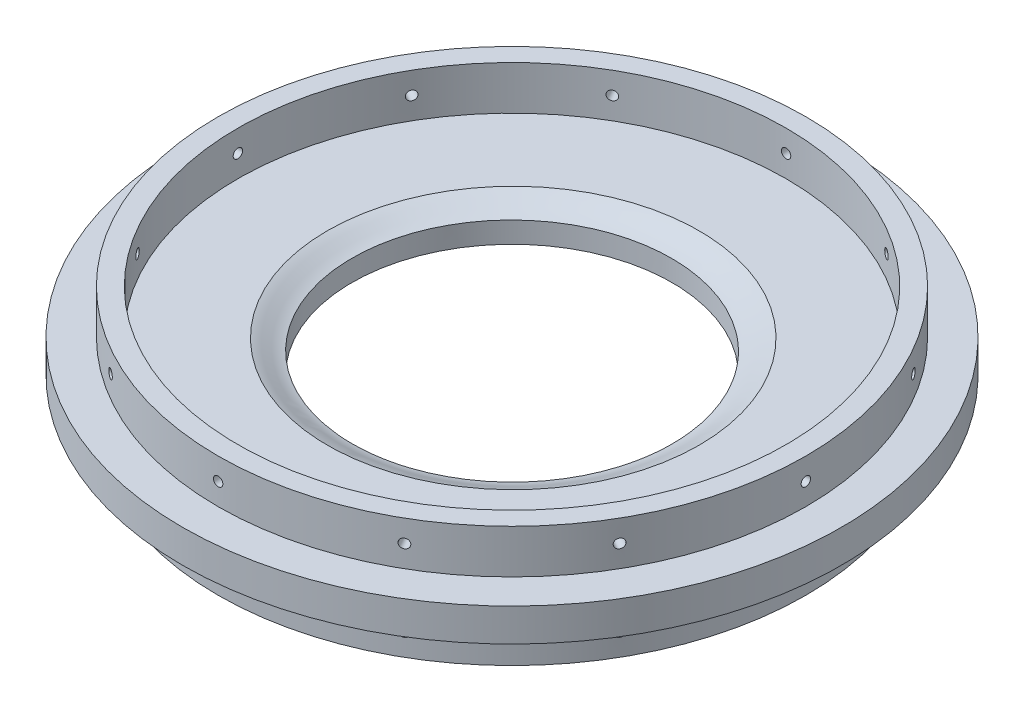
SolidWorks part; units mm, degrees
material "6061-T6 (SS)"
ref_plane "Front Plane" through (0, 0, 0) normal (0, 0, 1) x (1, 0, 0)
ref_plane "Top Plane" through (0, 0, 0) normal (0, 1, 0) x (1, 0, 0)
ref_plane "Right Plane" through (0, 0, 0) normal (1, 0, 0) x (0, 0, -1)
sketch "Sketch1" plane through (0, 0, 0) normal (0, 1, 0) x (1, 0, 0)
  line L5 (0, 0) -> (127.635, 0)
  line L6 (0, 0) -> (0, 127.635)
  line L7 (0, 127.635) -> (127.635, 127.635)
  line L8 (127.635, 0) -> (127.635, 127.635)
  dimension "D1" = 127.635
  dimension "D2" = 127.635
extrude "Boss-Extrude1" add sketch "Sketch1" along normal blind 9.525 contours L5 L8 L7 L6
sketch "Sketch12" plane through (0, 0, 0) normal (0, -1, 0) x (1, 0, 0)
  line L0 (63.8175, 0) -> (63.8175, -127.635) construction
  line L1 (0, 0) -> (127.635, 0) construction
  line L2 (0, -127.635) -> (127.635, -127.635) construction
  line L3 (0, -63.8175) -> (127.635, -63.8175) construction
  line L4 (0, 0) -> (0, -127.635) construction
  line L5 (127.635, 0) -> (127.635, -127.635) construction
  circle A0 centre (63.8175, -63.8175) radius 95.4151
  dimension "D1" = 190.8302
extrude "Boss-Extrude2" add sketch "Sketch12" against normal up to surface (9.525 mm away) contours A0 up to face at (63.8175, 9.525, -63.8175)
sketch "Sketch5" plane through (0, 9.525, 0) normal (0, 1, 0) x (1, 0, 0)
  circle A0 centre (63.8175, 63.8175) radius 46.355
  circle A3 centre (63.8175, 63.8175) radius 95.4151 construction
  dimension "D1" = 92.71
extrude "Cut-Extrude1" cut sketch "Sketch5" against normal blind 9.525
sketch "Sketch14" plane through (0, 9.525, 0) normal (0, -1, 0) x (1, 0, 0)
  line L0 (63.8175, -63.8175) -> (147.6375, -63.8175) construction
  line L1 (0, -19.2087) -> (0, 19.2087) construction
  line L2 (147.6375, -63.8175) -> (152.7175, -63.8175)
  line L3 (136.3808, -105.7742) -> (140.8401, -108.2104)
  circle A0 centre (63.8175, -63.8175) radius 46.355 construction
  arc A2 (147.6375, -63.8175) -> (136.3808, -105.7742) centre (63.8175, -63.8175) cw
  arc A3 (152.7175, -63.8175) -> (140.8401, -108.2104) centre (63.8175, -63.8175) cw
  point P0 (63.8175, -63.8175)
  dimension "D1" = 83.82
  dimension "D2" = 88.9
  dimension "D3" = 46.482
  dimension "D4" = 43.942
ref_plane "Support mirror reference plane" through (0, 4.7625, 0) normal (0, 1, 0) x (1, 0, 0)
sketch "Sketch25" plane through (0, 9.525, 0) normal (0, -1, 0) x (1, 0, 0)
  line L0 (63.8175, -63.8175) -> (123.0872, -4.5478) construction
  line L2 (123.0872, -4.5478) -> (126.6793, -0.9557)
  line L3 (144.7953, -42.1754) -> (149.6712, -40.7448)
  line L5 (63.8175, -63.8175) -> (147.6375, -63.8175) construction
  arc A2 (123.0872, -4.5478) -> (144.7953, -42.1754) centre (63.8175, -63.8175) cw
  arc A3 (126.6793, -0.9557) -> (149.6712, -40.7448) centre (63.8175, -63.8175) cw
  point P0 (63.8175, -63.8175)
  dimension "D1" = 83.82
  dimension "D2" = 88.9
  dimension "D3" = 46.482
  dimension "D4" = 43.942
  dimension "D5" = 45
sketch "Sketch30" plane through (0, 0, 0) normal (0, -1, 0) x (1, 0, 0)
  circle A0 centre (63.8175, -63.8175) radius 85.09
  circle A1 centre (63.8175, -63.8175) radius 79.375
  dimension "D1" = 170.18
  dimension "D2" = 158.75
extrude "Boss-Extrude3" add sketch "Sketch30" along normal blind 12.7
mirror "Mirror1" about plane through (0, 4.7625, 0) normal (0, 1, 0) of "Boss-Extrude3"
sketch "Sketch31" plane through (0, 0, 0) normal (0, -1, 0) x (-1, 0, 0)
  line L0 (-63.8175, -52.481) -> (-63.8175, 177.7216) construction
ref_plane "Plane1" through (0, 0, -148.9075) normal (0, 0, -1) x (-1, 0, 0)
ref_plane "Plane2" through (63.8175, 0, 0) normal (-1, 0, 0) x (0, 0, -1)
sketch "Sketch32" plane through (0, 0, -148.9075) normal (0, 0, -1) x (-1, 0, 0)
  line L4 (-63.8175, -87.3125) -> (-63.8175, 87.3125) construction
  line L5 (-148.9075, 0) -> (21.2725, 0) construction
  line L6 (21.2725, 9.525) -> (-148.9075, 9.525) construction
  circle A0 centre (-63.8175, -6.35) radius 1.3526
  circle A1 centre (-63.8175, 15.875) radius 1.3525
  dimension "D1" = 2.7051
  dimension "D2" = 2.7051
  dimension "D3" = 6.35
  dimension "D4" = 6.35
extrude "Cut-Extrude4" cut sketch "Sketch32" against normal blind 15.24
pattern_circular "CirPattern2" count 12 over 360 about axis through (63.8175, -12.7, -63.8175) along (0, 1, 0) of "Cut-Extrude4"
ref_plane "Plane3" through (0, 0, -63.754) normal (0, 0, 1) x (1, 0, 0)
sketch "Sketch35" plane through (0, 0, -63.754) normal (0, 0, 1) x (1, 0, 0)
  line L1 (118.0423, 9.525) -> (109.7873, 9.525)
  line L3 (110.1725, 9.525) -> (17.4625, 9.525) construction
  line L4 (17.4625, 0) -> (110.1725, 0) construction
  line L5 (17.4625, 0) -> (110.1725, 0)
  line L6 (64.2379, -16.1799) -> (64.2379, 15.7632) construction
  line L7 (109.7873, 9.525) -> (109.7873, 5.81)
  spline S0 degree 3 poles (118.0423, 9.525) (115.2087, 8.4474) (112.8295, 6.3493) (109.7873, 5.81) knots 0 0 0 0 1 1 1 1
  dimension "D2" = 8.255
revolve "Cut-Revolve1" cut sketch "Sketch35" angle 360 about L6 region at (112.545, 8.1821, -63.754)
